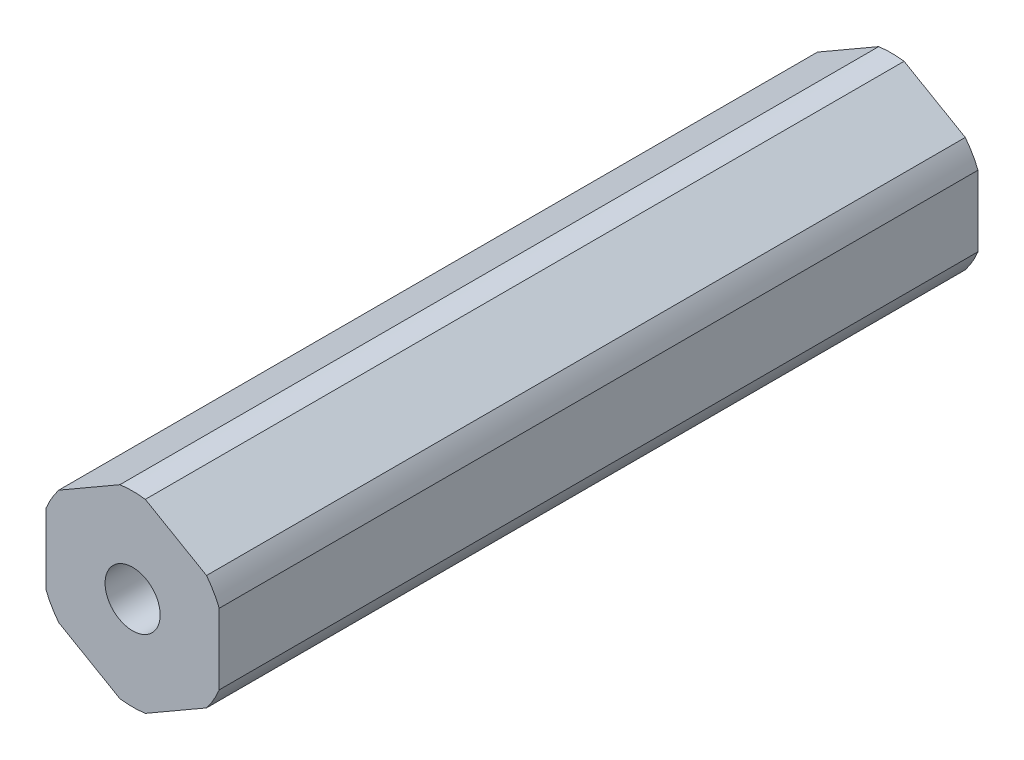
SolidWorks part; units mm, degrees
material "6061-T6 (SS)"
ref_plane "Front Plane" through (0, 0, 0) normal (0, 0, 1) x (1, 0, 0)
ref_plane "Top Plane" through (0, 0, 0) normal (0, 1, 0) x (1, 0, 0)
ref_plane "Right Plane" through (0, 0, 0) normal (1, 0, 0) x (0, 0, -1)
sketch "Sketch1" plane through (0, 0, 0) normal (0, 0, 1) x (1, 0, 0)
  line L1 (-0.9317, 6.7944) -> (-5.4183, 4.2041)
  line L2 (-6.35, 2.5903) -> (-6.35, -2.5903)
  line L3 (-5.4183, -4.2041) -> (-0.9317, -6.7944)
  line L4 (0.9317, -6.7944) -> (5.4183, -4.2041)
  line L5 (6.35, -2.5903) -> (6.35, 2.5903)
  line L6 (5.4183, 4.2041) -> (0.9317, 6.7944)
  circle A0 centre (0, 0) radius 6.35 construction
  arc A1 (-6.35, -2.5903) -> (-5.4183, -4.2041) centre (0, 0) ccw
  arc A2 (-0.9317, -6.7944) -> (0.9317, -6.7944) centre (0, 0) ccw
  arc A3 (5.4183, -4.2041) -> (6.35, -2.5903) centre (0, 0) ccw
  arc A4 (6.35, 2.5903) -> (5.4183, 4.2041) centre (0, 0) ccw
  arc A5 (0.9317, 6.7944) -> (-0.9317, 6.7944) centre (0, 0) ccw
  arc A6 (-5.4183, 4.2041) -> (-6.35, 2.5903) centre (0, 0) ccw
  dimension "D1" = 12.7
  dimension "D2" = 13.716
extrude "Boss-Extrude1" add sketch "Sketch1" along normal blind 55.626
sketch "Sketch2" plane through (0, 0, 55.626) normal (0, 0, 1) x (1, 0, 0)
  circle A0 centre (0, 0) radius 2.0193
  dimension "D1" = 4.0386
extrude "Cut-Extrude1" cut sketch "Sketch2" against normal through all
